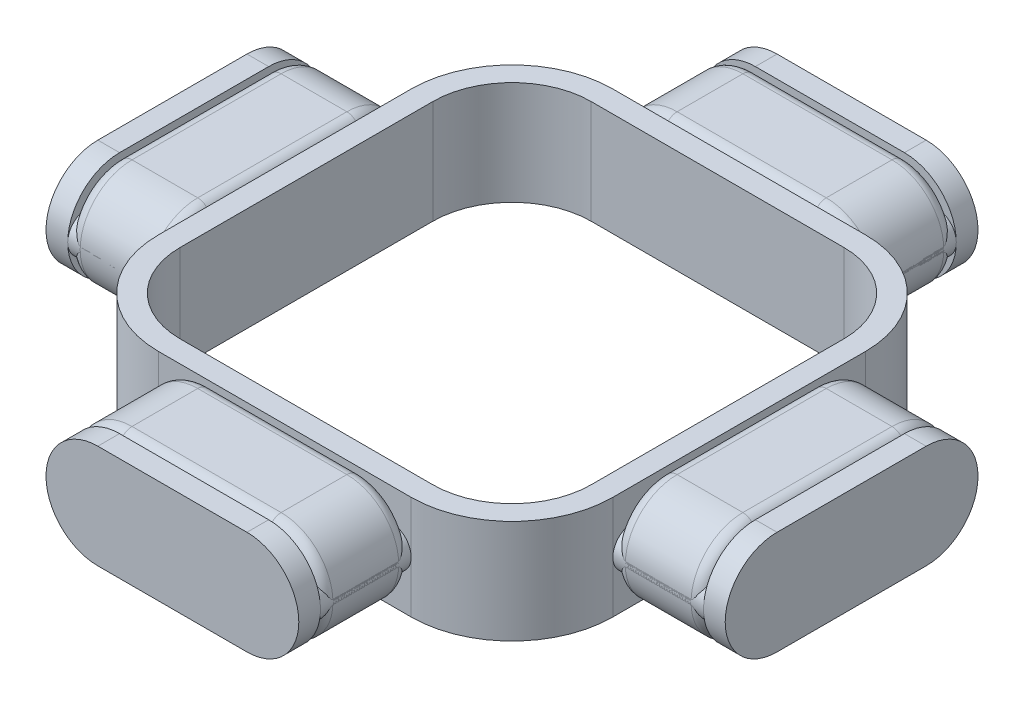
SolidWorks part; units mm, degrees
ref_plane "Front Plane" through (0, 0, 0) normal (0, 0, 1) x (1, 0, 0)
ref_plane "Top Plane" through (0, 0, 0) normal (0, 1, 0) x (1, 0, 0)
ref_plane "Right Plane" through (0, 0, 0) normal (1, 0, 0) x (0, 0, -1)
sketch "Sketch1" plane through (0, 0, 0) normal (0, 1, 0) x (1, 0, 0)
  line L0 (-33, 33) -> (33, 33)
  line L1 (39, 39) -> (-39, 39) construction
  line L2 (39, 39) -> (39, -39) construction
  line L3 (39, -39) -> (-39, -39) construction
  line L4 (-39, 39) -> (-39, -39) construction
  line L5 (39, 39) -> (-39, -39) construction
  line L6 (39, -39) -> (-39, 39) construction
  line L7 (-45, -45) -> (45, -45)
  line L8 (-45, -45) -> (-45, 45)
  line L9 (-45, 45) -> (45, 45)
  line L10 (45, -45) -> (45, 45)
  line L11 (-45, -45) -> (45, 45) construction
  line L12 (-45, 45) -> (45, -45) construction
  line L13 (33, -33) -> (33, 33)
  line L14 (-33, -33) -> (33, -33)
  line L15 (-33, -33) -> (-33, 33)
  circle A0 centre (39, 39) radius 2.75
  circle A1 centre (39, -39) radius 2.75
  circle A2 centre (-39, -39) radius 2.75
  circle A3 centre (-39, 39) radius 2.75
  point P0 (0, 0)
  point P6 (0, 0)
  dimension "D3" = 5.5
  dimension "D1" = 78
  dimension "D2" = 90
  dimension "D4" = 12
ref_axis "Axis1" through (0, 57.2807, 0) along (0, -1, 0)
sketch "Sketch4" plane through (0, 0, 0) normal (1, 0, 0) x (0, 0, -1)
  line L15 (-51.0432, 0) -> (-54.5291, 0)
  line L16 (-33, -8.3236) -> (-54.5291, -8.3236) construction
  line L17 (-33, -16.6473) -> (-33, 0)
  line L18 (-33, 0) -> (-36.4859, 0)
  line L19 (-54.5291, -16.6473) -> (-54.5291, 0)
  line L21 (-51.0432, 0) -> (-51.0432, -5.0977)
  line L22 (-51.0432, -5.0977) -> (-36.4859, -5.0977)
  line L23 (-36.4859, 0) -> (-36.4859, -5.0977)
  line L24 (-51.0432, 0) -> (-36.4859, 0) construction
  line L25 (-51.0432, -16.6473) -> (-54.5291, -16.6473)
  line L26 (-51.0432, -16.6473) -> (-51.0432, -11.5496)
  line L27 (-51.0432, -11.5496) -> (-36.4859, -11.5496)
  line L28 (-36.4859, -16.6473) -> (-36.4859, -11.5496)
  line L29 (-33, -16.6473) -> (-36.4859, -16.6473)
  line L30 (-45, 0) -> (45, 0) construction
  point P14 (-33.7109, 0)
extrude "Boss-Extrude3" add sketch "Sketch4" along normal mid plane 40.59
fillet "Fillet1" 2 edges at (20.295, -5.0977, 43.7646) (20.295, -11.5496, 43.7646) type full round first side face at (0, -5.0977, 43.7646) second side face at (0, -11.5496, 43.7646) middle face at (20.295, -8.3236, 43.7646)
fillet "Fillet2" 2 edges at (-20.295, -5.0977, 43.7646) (-20.295, -11.5496, 43.7646) type full round first side face at (-1.613, -5.0977, 43.7646) second side face at (-1.613, -11.5496, 43.7646) middle face at (-20.295, -8.3236, 43.7646)
fillet "Fillet5" 2 edges at (20.295, 0, 52.7862) (20.295, -16.6473, 52.7862) type full round first side face at (0, 0, 52.7862) second side face at (0, -16.6473, 52.7862) middle face at (20.295, -8.3236, 52.4376)
fillet "Fillet6" 2 edges at (-20.295, 0, 52.7862) (-20.295, -16.6473, 52.7862) type full round first side face at (-4.1618, 0, 52.7862) second side face at (-4.1618, -16.6473, 52.7862) middle face at (-20.295, -8.3236, 52.4376)
pattern_circular "CirPattern3" count 4 over 360 about axis through (0, 57.2807, 0) along (0, -1, 0) of bodies 119
sketch "Sketch7" plane through (0, 0, 0) normal (0, 1, 0) x (1, 0, 0)
  line L0 (33, -20.295) -> (20.295, -20.295) construction
  line L1 (20.295, -20.295) -> (20.295, -33) construction
  line L12 (-20.295, 36.4859) -> (20.295, 36.4859) construction
  line L13 (-20.295, 33) -> (20.295, 33) construction
  line L14 (-36.4859, -20.295) -> (-36.4859, 20.295) construction
  line L15 (-33, -20.295) -> (-33, 20.295) construction
  line L16 (20.295, -36.4859) -> (-20.295, -36.4859) construction
  line L17 (20.295, -33) -> (-20.295, -33) construction
  line L18 (33, 20.295) -> (33, -20.295) construction
  line L19 (36.4859, 20.295) -> (36.4859, -20.295) construction
  line L20 (-20.295, 36.4859) -> (20.295, 36.4859)
  line L21 (-20.295, 33) -> (20.295, 33)
  line L22 (-36.4859, -20.295) -> (-36.4859, 20.295)
  line L23 (-33, -20.295) -> (-33, 20.295)
  line L24 (20.295, -36.4859) -> (-20.295, -36.4859)
  line L25 (20.295, -33) -> (-20.295, -33)
  line L26 (33, 20.295) -> (33, -20.295)
  line L27 (36.4859, 20.295) -> (36.4859, -20.295)
  arc A0 (20.295, -33) -> (33, -20.295) centre (20.295, -20.295) ccw
  arc A1 (20.295, -36.4859) -> (36.4859, -20.295) centre (20.295, -20.295) ccw
  arc A2 (-33, -20.295) -> (-20.295, -33) centre (-20.295, -20.295) ccw
  arc A3 (-36.4859, -20.295) -> (-20.295, -36.4859) centre (-20.295, -20.295) ccw
  arc A4 (-20.295, 33) -> (-33, 20.295) centre (-20.295, 20.295) ccw
  arc A5 (-20.295, 36.4859) -> (-36.4859, 20.295) centre (-20.295, 20.295) ccw
  arc A6 (33, 20.295) -> (20.295, 33) centre (20.295, 20.295) ccw
  arc A7 (36.4859, 20.295) -> (20.295, 36.4859) centre (20.295, 20.295) ccw
  dimension "D1" = 4
extrude "Boss-Extrude4" add sketch "Sketch7" against normal up to surface (16.6473 mm away) up to face at (34.7429, -16.6473, 0)
sketch "Sketch9" plane through (0, 0, 36.4859) normal (0, 0, 1) x (1, 0, 0)
  line L0 (-30.8675, -8.3236) -> (30.8675, -8.3236) construction
  line L1 (-11.9714, -8.3236) -> (11.9714, -8.3236) construction
  line L2 (-11.9714, 0) -> (11.9714, 0)
  line L3 (-11.9714, -16.6473) -> (11.9714, -16.6473)
  arc A0 (-11.9714, 0) -> (-11.9714, -16.6473) centre (-11.9714, -8.3236) ccw
  arc A1 (11.9714, -16.6473) -> (11.9714, 0) centre (11.9714, -8.3236) ccw
  arc A2 (11.9714, -16.6473) -> (11.9714, 0) centre (11.9714, -8.3236) ccw construction
  point P6 (0, -8.3236)
  point P12 (0, 0)
  point P13 (17.5384, -8.3236)
  point P14 (17.5898, -0.5647)
extrude "Boss-Extrude5" add sketch "Sketch9" along normal up to surface (14.5573 mm away) separate body up to face at (0, -3.6764, 51.0432)
fillet "Fillet3" radius 2 8 edges at (0, -16.6473, 51.0432) (-20.295, -8.3236, 51.0432) (0, 0, 51.0432) (0, -16.6473, 36.4859) (-20.295, -8.3236, 36.4859) (0, 0, 36.4859) (20.295, -8.3236, 51.0432) (20.295, -8.3236, 36.4859)
pattern_circular "CirPattern5" count 4 over 360 about axis through (0, 57.2807, 0) along (0, -1, 0) of bodies 127
